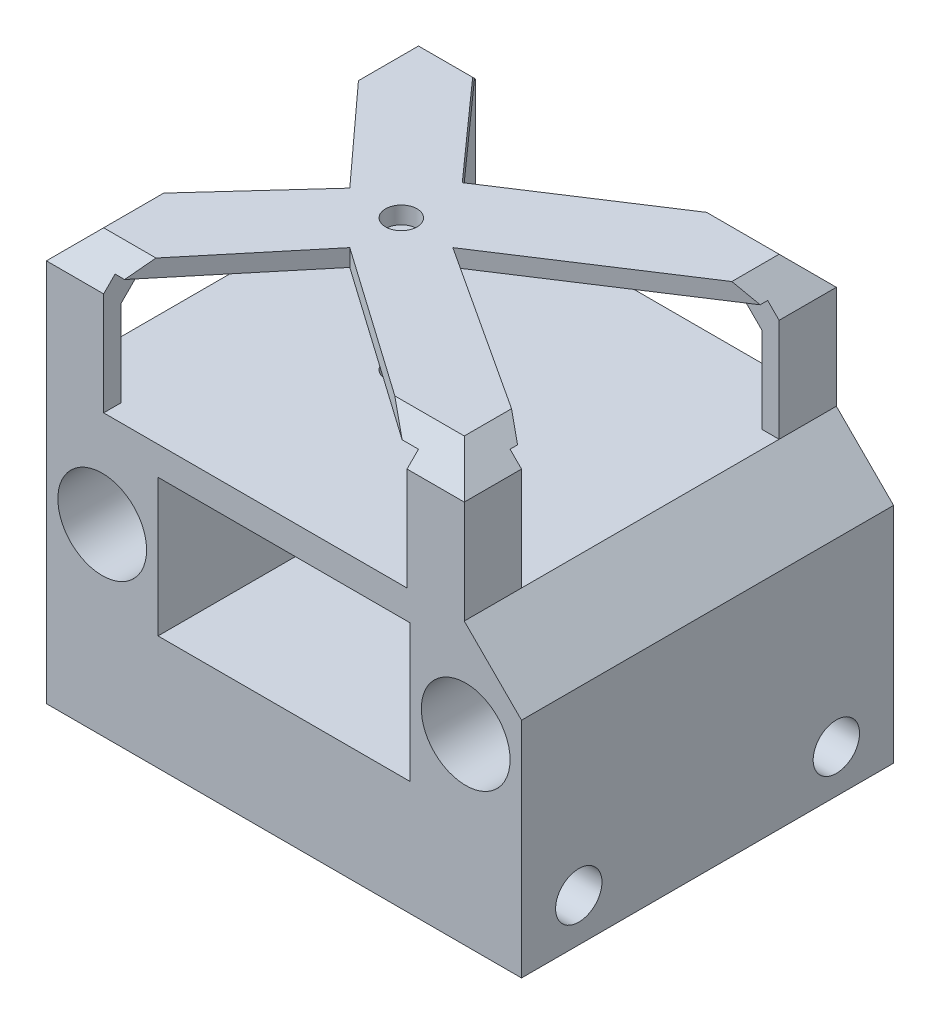
SolidWorks part; units mm, degrees
ref_plane "Front Plane" through (0, 0, 0) normal (0, 0, 1) x (1, 0, 0)
ref_plane "Top Plane" through (0, 0, 0) normal (0, 1, 0) x (1, 0, 0)
ref_plane "Right Plane" through (0, 0, 0) normal (1, 0, 0) x (0, 0, -1)
sketch "Sketch1" plane through (0, 0, 0) normal (0, 0, 1) x (1, 0, 0)
  line L0 (31.75, 17) -> (-31.75, 17)
  line L1 (-22, -12) -> (22, -12)
  line L2 (-22, -12) -> (-22, 12)
  line L3 (-22, 12) -> (22, 12)
  line L4 (22, -12) -> (22, 12)
  line L5 (-22, -12) -> (22, 12) construction
  line L6 (-22, 12) -> (22, -12) construction
  line L7 (-31.75, -17) -> (31.75, -17)
  line L8 (31.75, -17) -> (41.5, -17)
  line L9 (41.5, 17) -> (31.75, 17)
  line L10 (-31.75, -17) -> (-41.5, -17)
  line L11 (-41.5, -17) -> (-41.5, 17)
  line L12 (0, 0) -> (0, 8.5) construction
  line L13 (41.5, -17) -> (41.5, 17)
  line L15 (-41.5, 17) -> (-31.75, 17)
  circle A0 centre (-31.75, 0) radius 7.75
  circle A1 centre (31.75, 0) radius 7.75
  point P0 (0, 0)
  point P8 (-22, 0)
  point P12 (22, 0)
  dimension "D3" = 15.5
  dimension "D5" = 15.5
  dimension "D1" = 44
  dimension "D2" = 24
  dimension "D4" = 9.75
  dimension "D6" = 9.75
  dimension "D7" = 5
  dimension "D8" = 5
  dimension "D9" = 9.75
extrude "Boss-Extrude1" add sketch "Sketch1" along normal blind 65
sketch "Sketch5" plane through (41.5, 0, 0) normal (1, 0, 0) x (0, 0, -1)
  line L0 (-65, -17) -> (0, -17)
  line L1 (0, -17) -> (0, -32)
  line L2 (0, -32) -> (-65, -32)
  line L3 (-65, -32) -> (-65, -17)
  line L4 (-65, -24.5) -> (-55, -24.5) construction
  line L5 (-55, -24.5) -> (-10, -24.5) construction
  line L6 (-10, -24.5) -> (0, -24.5) construction
  circle A0 centre (-55, -24.5) radius 4.05
  circle A1 centre (-10, -24.5) radius 4.05
  dimension "D1" = 8.1
  dimension "D2" = 8.1
  dimension "D3" = 45
  dimension "D4" = 15
extrude "Boss-Extrude4" add sketch "Sketch5" against normal up to surface (83 mm away) up to face at (-41.5, 0, 32.5)
chamfer "Chamfer1" distance 10 angle 45 1 edges at (41.5, 17, 32.5)
sketch "Sketch6" plane through (0, 12, 0) normal (0, -1, 0) x (-1, 0, 0)
  line L0 (0, -65) -> (0, 0) construction
  line L1 (-22, -65) -> (22, -65) construction
  line L2 (-22, 0) -> (22, 0) construction
  circle A0 centre (12, -32.5) radius 2.75
  point P8 (0, -32.5)
  dimension "D1" = 5.5
  dimension "D2" = 12
extrude "Cut-Extrude1" cut sketch "Sketch6" against normal blind 15
ref_plane "Plane2" through (0, 37, 0) normal (0, 1, 0) x (1, 0, 0)
sketch "Sketch8" plane through (0, 37, 0) normal (0, 1, 0) x (1, 0, 0)
  line L0 (-41.5, -10) -> (-21, -32.5)
  line L1 (-21, -32.5) -> (-41.5, -55)
  line L2 (-12, -41.5) -> (-31.5, -65)
  line L3 (-12, -21.8478) -> (-31.5, 0)
  line L4 (-41.5, -65) -> (31.5, -65)
  line L5 (31.5, -65) -> (31.5, 0)
  line L6 (31.5, 0) -> (-41.5, 0)
  line L7 (-41.5, 0) -> (-41.5, -65)
  line L8 (-41.5, -65) -> (-31.5, -65)
  line L9 (31.5, -65) -> (31.5, -55)
  line L10 (31.5, 0) -> (21.5, 0)
  line L11 (-41.5, 0) -> (-41.5, -10)
  line L12 (-12, -21.8478) -> (21.5, 0)
  line L13 (-3, -32.5) -> (31.5, -10)
  line L14 (-3, -32.5) -> (31.5, -55)
  line L15 (-12, -41.5) -> (21.5, -65)
  line L16 (-31.5, 0) -> (-41.5, 0)
  line L17 (-41.5, -55) -> (-41.5, -65)
  line L18 (21.5, -65) -> (31.5, -65)
  line L19 (31.5, -10) -> (31.5, 0)
  circle A0 centre (-12, -32.5) radius 2.75
  dimension "D2" = 5.5
  dimension "D4" = 10
  dimension "D1" = 0
extrude "Boss-Extrude5" add sketch "Sketch8" along normal blind 3 separate body
sketch "Sketch9" plane through (0, 37, 0) normal (0, -1, 0) x (-1, 0, 0)
  line L0 (41.5, -10) -> (41.5, 0)
  line L1 (41.5, 0) -> (31.5, 0)
  line L2 (-21.5, 0) -> (-31.5, 0)
  line L3 (-31.5, 0) -> (-31.5, -10)
extrude "Extrude-Thin2" add sketch "Sketch9" along normal up to surface (20 mm away) thin up to face at (-9.25, 17, 32.5) thin type one direction reverse wall 3
ref_plane "Plane3" through (0, 0, 32.5) normal (0, 0, 1) x (1, 0, 0)
mirror "Mirror1" about plane through (0, 0, 32.5) normal (0, 0, 1) of "Extrude-Thin2"
chamfer "Chamfer2" distance 5 angle 45 8 edges at (28.5, 37, 58.5) (25, 37, 62) (28.5, 37, 6.5) (25, 37, 3) (-35, 37, 3) (-38.5, 37, 6.5) (-38.5, 37, 58.5) (-35, 37, 62)
chamfer "Chamfer3" distance 5 angle 45 8 edges at (-36.5, 40, 65) (-41.5, 40, 60) (-36.5, 40, 0) (-41.5, 40, 5) (26.5, 40, 0) (31.5, 40, 5) (26.5, 40, 65) (31.5, 40, 60)
